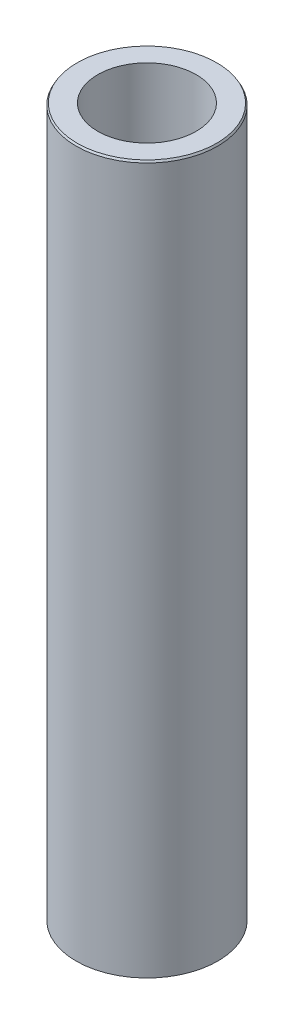
SolidWorks part; units mm, degrees
ref_plane "Front Plane" through (0, 0, 0) normal (0, 0, 1) x (1, 0, 0)
ref_plane "Top Plane" through (0, 0, 0) normal (0, 1, 0) x (1, 0, 0)
ref_plane "Right Plane" through (0, 0, 0) normal (1, 0, 0) x (0, 0, -1)
sketch "Sketch1" plane through (0, 0, 0) normal (0, 1, 0) x (1, 0, 0)
  circle A0 centre (0, 0) radius 60
  dimension "SHAFT_OD" = 120
extrude "Boss-Extrude1" add sketch "Sketch1" along normal blind 600
sketch "Sketch2" plane through (0, 0, 0) normal (0, 1, 0) x (1, 0, 0)
  circle A0 centre (0, 0) radius 41.6331
  dimension "BORE_D" = 83.2663
extrude "Cut-Extrude1" cut sketch "Sketch2" along normal through all
chamfer "Chamfer1" distance 1.6151 angle 30 2 edges at (0, 600, 60) (0, 0, 60) first distance on face at (0, 600, 60) first distance on face at (0, 0, 41.6331)
